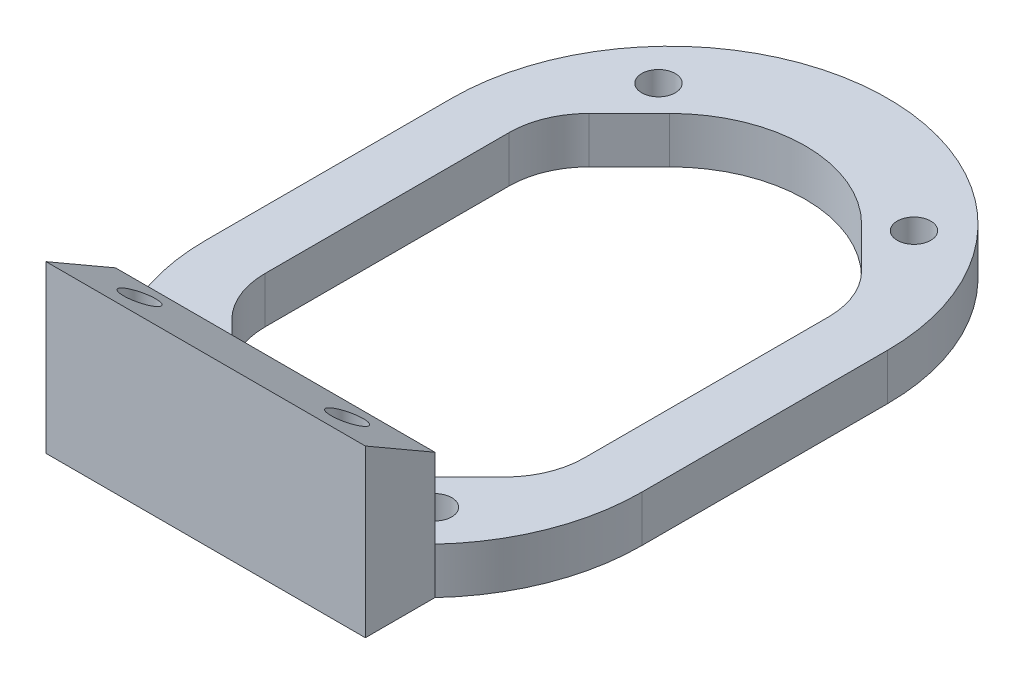
SolidWorks part; units mm, degrees
ref_plane "Front Plane" through (0, 0, 0) normal (0, 0, 1) x (1, 0, 0)
ref_plane "Top Plane" through (0, 0, 0) normal (0, 1, 0) x (1, 0, 0)
ref_plane "Right Plane" through (0, 0, 0) normal (1, 0, 0) x (0, 0, -1)
sketch "Outline" plane through (0, 0, 0) normal (0, 1, 0) x (1, 0, 0)
  line L1 (10, -17) -> (-10, -17)
  line L2 (10, -17) -> (10, 17)
  line L3 (10, 17) -> (-10, 17)
  line L4 (-10, -17) -> (-10, 17)
  line L5 (10, -17) -> (-10, 17) construction
  line L6 (10, 17) -> (-10, -17) construction
  point P0 (0, 0)
  dimension "D1" = 20
  dimension "D2" = 34
sketch "MountingHoles" plane through (0, 0, 0) normal (0, 1, 0) x (1, 0, 0)
  line L1 (8, -15) -> (-8, -15)
  line L2 (8, -15) -> (8, 15)
  line L3 (8, 15) -> (-8, 15)
  line L4 (-8, -15) -> (-8, 15)
  line L5 (8, -15) -> (-8, 15) construction
  line L6 (8, 15) -> (-8, -15) construction
  circle A0 centre (-8, 15) radius 1.05
  circle A1 centre (8, 15) radius 1.05
  circle A2 centre (-8, -15) radius 1.05
  circle A3 centre (8, -15) radius 1.05
  point P8 (0, 0)
  dimension "D1" = 2.1
  dimension "D2" = 30
  dimension "D3" = 16
sketch "Horn" plane through (0, 0, 0) normal (0, 1, 0) x (1, 0, 0)
  line L0 (10, 17) -> (-10, 17) construction
  line L3 (0, -1000) -> (0, 49000) construction
  line L4 (10, 17) -> (-10, -17) construction
  circle A0 centre (0, 7.7) radius 8
  point P17 (0, 0)
  dimension "D1" = 16
  dimension "D2" = 9.3
sketch "WireCutout" plane through (0, 0, 0) normal (0, 1, 0) x (1, 0, 0)
  line L0 (-10, -17) -> (-10, 17) construction
  line L1 (-10, -7.15) -> (-5.8, -7.15)
  line L2 (-10, -7.15) -> (-10, 4.15)
  line L3 (-10, 4.15) -> (-5.8, 4.15)
  line L4 (-5.8, -7.15) -> (-5.8, 4.15)
  line L5 (10, -17) -> (10, 17) construction
  line L6 (10, 4.15) -> (5.8, 4.15)
  line L7 (10, 4.15) -> (10, -7.15)
  line L8 (10, -7.15) -> (5.8, -7.15)
  line L9 (5.8, 4.15) -> (5.8, -7.15)
  line L10 (10, 17) -> (-10, 17) construction
  line L11 (10, -17) -> (-10, -17) construction
  dimension "D1" = 12.85
  dimension "D2" = 9.85
  dimension "D3" = 4.2
sketch "Sketch26" plane through (0, 0, 0) normal (0, 1, 0) x (1, 0, 0)
  line L0 (0, -201000) -> (0, 249000) construction
  line L1 (-1000, 0) -> (49000, 0) construction
  line L2 (-13.6561, -7.7) -> (-13.6561, 7.7)
  line L3 (-8.5, 7.7) -> (-8.5, -7.7)
  line L4 (8.5, -7.7) -> (8.5, 7.7)
  line L5 (13.6561, 7.7) -> (13.6561, -7.7)
  arc A0 (-13.6561, 7.7) -> (13.6561, 7.7) centre (0, 7.7) cw
  arc A1 (-8.5, 7.7) -> (8.5, 7.7) centre (0, 7.7) cw
  arc A2 (-13.6561, -7.7) -> (13.6561, -7.7) centre (0, -7.7) ccw
  arc A3 (-8.5, -7.7) -> (8.5, -7.7) centre (0, -7.7) ccw
  circle A4 centre (0, 7.7) radius 8 construction
  point P0 (0, -7.7)
  dimension "D1" = 0.5
extrude "Boss-Extrude6" add sketch "Sketch26" along normal blind 2.9
sketch "Sketch27" plane through (0, 2.9, 0) normal (0, 1, 0) x (1, 0, 0)
  circle A0 centre (-8, 15) radius 1.05
  circle A1 centre (8, 15) radius 1.05
  circle A2 centre (8, -15) radius 1.05
  circle A3 centre (-8, -15) radius 1.05
  circle A4 centre (-8, -15) radius 1.05 construction
  circle A5 centre (8, -15) radius 1.05 construction
  circle A6 centre (8, 15) radius 1.05 construction
  circle A7 centre (-8, 15) radius 1.05 construction
extrude "Cut-Extrude12" cut sketch "Sketch27" against normal through all
sketch "Sketch29" plane through (0, 2.9, 0) normal (0, 1, 0) x (1, 0, 0)
  line L0 (-10, -17) -> (10, -17)
  line L1 (-996.0655, -21.3561) -> (49003.9345, -21.3561) construction
  line L2 (-10, -17) -> (-10, -21.3561)
  line L3 (10, -17) -> (10, -21.3561)
  line L4 (10, -21.3561) -> (-10, -21.3561)
  arc A2 (-13.6561, -7.7) -> (13.6561, -7.7) centre (0, -7.7) ccw construction
extrude "Boss-Extrude8" add sketch "Sketch29" along normal blind 11.5 and the other way up to surface (2.9 mm away) other way up to face at (-8, 0, 16.05)
sketch "Sketch33" plane through (10, 0, 0) normal (1, 0, 0) x (0, 0, -1)
  line L0 (-21.3561, 14.4) -> (-21.3561, 10.4)
  line L1 (-21.3561, 0) -> (-21.3561, 14.4) construction
  line L2 (-21.3561, 10.4) -> (-17, 7.885)
  line L3 (-17, 2.9) -> (-17, 14.4) construction
  line L4 (-17, 7.885) -> (-17, 14.4)
  line L5 (-17, 14.4) -> (-21.3561, 14.4)
  dimension "D1" = 60
  dimension "D2" = 4
extrude "Cut-Extrude16" cut sketch "Sketch33" against normal through all
sketch "Sketch34" plane through (0, 0, 0) normal (0, -1, 0) x (1, 0, 0)
  line L2 (-1010, 17) -> (48990, 17) construction
  line L5 (0, -1000) -> (0, 49000) construction
  circle A0 centre (6.5, 19) radius 1
  circle A1 centre (-6.5, 19) radius 1
  dimension "D1" = 2
  dimension "D2" = 2
  dimension "D3" = 13
extrude "Cut-Extrude17" cut sketch "Sketch34" against normal through all
sketch "Sketch35" plane through (0, 2.9, 0) normal (0, 1, 0) x (1, 0, 0)
  line L0 (-10, 9.7208) -> (-10, -9.7208)
  line L1 (-10, -9.7208) -> (-6.0104, -13.7104)
  line L2 (-6.0104, -13.7104) -> (-6.0104, 13.7104)
  line L3 (-6.0104, 13.7104) -> (-10, 9.7208)
  line L4 (-10, -17) -> (-10, 17) construction
  arc A0 (8.5, 7.7) -> (-8.5, 7.7) centre (0, 7.7) ccw construction
  arc A3 (-8.5, -7.7) -> (8.5, -7.7) centre (0, -7.7) ccw construction
  dimension "D1" = 45
extrude "Cut-Extrude18" cut sketch "Sketch35" against normal through all
fillet "Fillet1" radius 5 2 edges at (-10, 1.45, 9.7208) (-10, 1.45, -9.7208)
mirror "Mirror1" about plane through (0, 0, 0) normal (1, 0, 0) of "Cut-Extrude18", "Fillet1"
